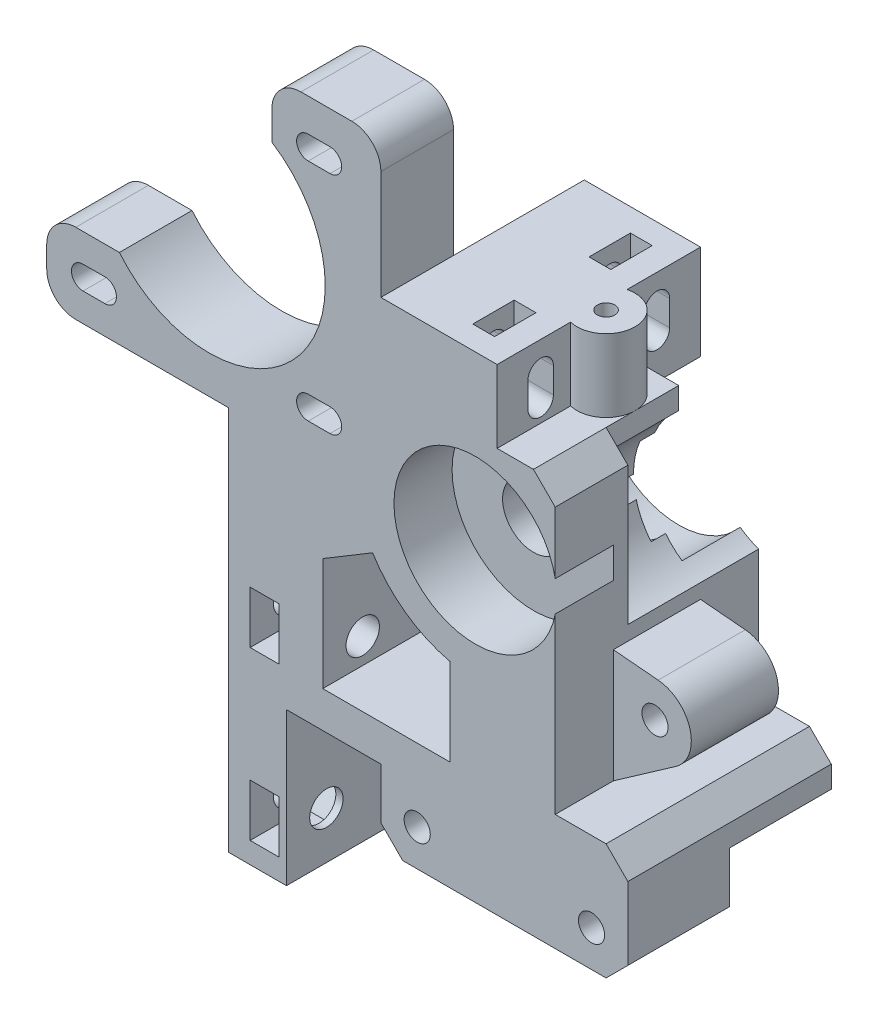
SolidWorks part; units mm, degrees
ref_plane "Front Plane" through (0, 0, 0) normal (0, 0, 1) x (1, 0, 0)
ref_plane "Top Plane" through (0, 0, 0) normal (0, 1, 0) x (1, 0, 0)
ref_plane "Right Plane" through (0, 0, 0) normal (1, 0, 0) x (0, 0, -1)
sketch "Sketch1" plane through (0, 0, 0) normal (0, 0, 1) x (1, 0, 0)
  line L0 (0, 0) -> (0, -11)
  line L1 (0, -11) -> (25, -11)
  line L2 (25, -11) -> (25, -64)
  line L3 (25, -64) -> (33, -64)
  line L4 (33, -64) -> (33, -43)
  line L5 (33, -43) -> (46, -43)
  line L6 (46, -43) -> (46, -53)
  line L7 (46, -53) -> (85, -53)
  line L8 (85, -53) -> (85, -43) construction
  line L9 (85, -43) -> (80, -43)
  line L10 (80, -43) -> (80, -37)
  line L11 (80, -37) -> (70, -37)
  line L12 (70, -37) -> (78.6011, -30.9774)
  line L13 (70, -37) -> (70, -21.361) construction
  line L14 (70, -21.361) -> (76.169, -21.9007)
  line L15 (70, -21.361) -> (70, 12.639)
  line L16 (70, 12.639) -> (46, 12.639)
  line L17 (46, 12.639) -> (46, 31.639)
  line L18 (46, 31.639) -> (31, 31.639)
  line L19 (31, 31.639) -> (31, 23.639)
  line L20 (0, 0) -> (10, 0)
  line L21 (38, -22.5) -> (38, -38)
  line L22 (38, -38) -> (55.5, -38)
  line L23 (55.5, -38) -> (55.5, -26)
  line L24 (38, -22.5) -> (44.8573, -18.3797)
  line L25 (85, -48) -> (46, -48) construction
  line L26 (25, -11) -> (59, -11) construction
  line L27 (5, -5.5) -> (8, -5.5) construction
  line L28 (5, -3.9) -> (8, -3.9)
  line L29 (5, -7.1) -> (8, -7.1)
  line L30 (36, -5.5) -> (39, -5.5) construction
  line L31 (36, -3.9) -> (39, -3.9)
  line L32 (36, -7.1) -> (39, -7.1)
  line L33 (36, 25.5) -> (39, 25.5) construction
  line L34 (36, 27.1) -> (39, 27.1)
  line L35 (36, 23.9) -> (39, 23.9)
  line L36 (5, -5.5) -> (36, -5.5) construction
  line L37 (36, -5.5) -> (36, 25.5) construction
  line L38 (5, -5.5) -> (0, -5.5) construction
  arc A0 (85, -53) -> (85, -43) centre (85, -48) ccw
  circle A1 centre (75.7332, -26.8817) radius 5
  arc A2 (10, 0) -> (31, 23.639) centre (22.3388, 10.186) ccw
  arc A3 (44.8573, -18.3797) -> (55.5, -26) centre (59.3127, -9.4331) ccw
  circle A4 centre (51, -48) radius 1.8
  circle A5 centre (75, -48) radius 1.8
  circle A6 centre (85, -48) radius 1.8
  circle A7 centre (75.7332, -26.8817) radius 1.8
  circle A8 centre (59, -11) radius 4.25
  arc A9 (5, -3.9) -> (5, -7.1) centre (5, -5.5) ccw
  arc A10 (8, -7.1) -> (8, -3.9) centre (8, -5.5) ccw
  arc A11 (36, -3.9) -> (36, -7.1) centre (36, -5.5) ccw
  arc A12 (39, -7.1) -> (39, -3.9) centre (39, -5.5) ccw
  arc A13 (36, 27.1) -> (36, 23.9) centre (36, 25.5) ccw
  arc A14 (39, 23.9) -> (39, 27.1) centre (39, 25.5) ccw
  point P45 (6.5, -5.5)
  point P50 (37.5, -5.5)
  point P57 (37.5, 25.5)
  dimension "D1" = 11
  dimension "D14" = 35
  dimension "D9" = 10
  dimension "D15" = 10
  dimension "D21" = 10
  dimension "D28" = 17
  dimension "D31" = 3.6
  dimension "D33" = 24
  dimension "D34" = 34
  dimension "D35" = 8.5
  dimension "D37" = 1.6
  dimension "D39" = 5
  dimension "D40" = 16
  dimension "D2" = 25
  dimension "D4" = 8
  dimension "D5" = 21
  dimension "D6" = 13
  dimension "D7" = 10
  dimension "D8" = 39
  dimension "D10" = 5
  dimension "D11" = 6
  dimension "D12" = 10
  dimension "D13" = 10.5
  dimension "D16" = 40
  dimension "D17" = 34
  dimension "D18" = 24
  dimension "D19" = 19
  dimension "D20" = 15
  dimension "D22" = 8
  dimension "D23" = 15.5
  dimension "D24" = 17.5
  dimension "D25" = 12
  dimension "D26" = 8
  dimension "D27" = 121
  dimension "D29" = 5
  dimension "D30" = 5
  dimension "D32" = 5
  dimension "D36" = 3
  dimension "D38" = 31
  dimension "D41" = 53
extrude "Boss-Extrude1" add sketch "Sketch1" against normal blind 34 contours A2 L20 L0 L1 L2 L3 L4 L5 L6 L7 A0 L9 L10 L11 L12 A1 L14 L15 L16 L17 L18 L19 A14 L35 A13 L34 A12 L32 A11 L31 A10 L29 A9 L28 A8 A6 A5 A4 L24 A3 L23 L22 L21 | A1 A7 region at (48.0686, -19.084, 0) region at (79.3153, -23.5993, 0)
sketch "Sketch7" plane through (0, 0, 0) normal (0, 0, 1) x (1, 0, 0)
  line L1 (70, -21.361) -> (80.7332, -21.361)
  line L2 (70, -21.361) -> (70, -37)
  line L3 (70, -37) -> (80.7332, -37)
  line L4 (80.7332, -21.361) -> (80.7332, -37)
  circle A0 centre (59, -11) radius 11.2
  arc A1 (78.6011, -30.9774) -> (76.169, -21.9007) centre (75.7332, -26.8817) ccw construction
  dimension "D1" = 22.4
extrude "Cut-Extrude5" cut sketch "Sketch7" against normal blind 8
sketch "Sketch2" plane through (25, 0, 0) normal (-1, 0, 0) x (0, 0, 1)
  line L0 (-28.5, -34.5) -> (-5.5, -34.5) construction
  line L1 (-5.5, -34.5) -> (-5.5, -57.5) construction
  line L2 (-5.5, -57.5) -> (-28.5, -57.5) construction
  line L3 (-28.5, -57.5) -> (-28.5, -34.5) construction
  line L4 (-17, -57.5) -> (-17, -64) construction
  line L5 (-34, -64) -> (0, -64) construction
  line L6 (-34, -24) -> (-28, -24)
  line L7 (-34, -11) -> (-34, -64) construction
  line L8 (-28, -24) -> (-28, 13.5)
  line L9 (-28, 13.5) -> (-10, 13.5)
  line L10 (-10, 13.5) -> (-10, 31.639)
  line L11 (-34, 31.639) -> (0, 31.639) construction
  line L12 (-10, 31.639) -> (-34, 31.639)
  line L13 (-34, 31.639) -> (-34, -24)
  circle A0 centre (-28.5, -34.5) radius 2.3
  circle A1 centre (-5.5, -34.5) radius 2.3
  circle A2 centre (-5.5, -57.5) radius 2.3
  circle A3 centre (-28.5, -57.5) radius 2.3
  dimension "D3" = 4.6
  dimension "D1" = 23
  dimension "D2" = 6.5
  dimension "D4" = 6
  dimension "D5" = 37.5
  dimension "D6" = 18
  dimension "D7" = 40
extrude "Cut-Extrude1" cut sketch "Sketch2" against normal blind 28
sketch "Sketch4" plane through (0, 0, -34) normal (0, 0, -1) x (-1, 0, 0)
  line L0 (-25, -24) -> (-46, -11.3806)
  line L1 (-46, -11.3806) -> (-46, 31.639)
  line L2 (-46, 31.639) -> (0, 31.639)
  line L3 (0, 31.639) -> (0, -11)
  line L4 (0, -11) -> (-25, -11)
  line L5 (-25, -11) -> (-25, -24)
  line L6 (-70, 12.639) -> (-67, 12.639)
  line L7 (-46, -53) -> (-85, -53) construction
  line L8 (-70, 12.639) -> (-70, -19.361)
  line L9 (-70, -21.361) -> (-70, 12.639) construction
  line L10 (-80, -43) -> (-90, -43)
  line L11 (-67, 12.639) -> (-67, -0.361)
  line L12 (-80, -43) -> (-80, -53)
  line L13 (-80, -53) -> (-90, -53)
  line L14 (-90, -43) -> (-90, -53)
  arc A0 (-70, -19.361) -> (-67, -0.361) centre (-73.7732, -9.0284) ccw
  arc A1 (-85, -43) -> (-85, -53) centre (-85, -48) ccw construction
  dimension "D4" = 11
  dimension "D1" = 24.5
  dimension "D2" = 3
  dimension "D3" = 32
  dimension "D5" = 13
extrude "Cut-Extrude2" cut sketch "Sketch4" against normal blind 24
sketch "Sketch5" plane through (0, 0, -34) normal (0, 0, -1) x (-1, 0, 0)
  line L0 (-33, -24) -> (-33, -64)
  line L1 (-25, -24) -> (-38, -24) construction
  line L2 (-33, -24) -> (0, -24)
  line L3 (0, -24) -> (0, 31.639)
  line L4 (0, 31.639) -> (-90, 31.639)
  line L5 (-90, 31.639) -> (-90, -64)
  line L6 (-90, -64) -> (-33, -64)
  line L7 (-46, 31.639) -> (-31, 31.639) construction
  line L9 (-25, -64) -> (-33, -64) construction
  line L10 (-33, -64) -> (-33, -43) construction
  arc A0 (-85, -43) -> (-85, -53) centre (-85, -48) ccw construction
extrude "Cut-Extrude3" cut sketch "Sketch5" against normal blind 6 contours L5 L6 L0 L2 L3 L4
sketch "Sketch6" plane through (0, 0, -34) normal (0, 0, -1) x (-1, 0, 0)
  line L0 (-67, 12.639) -> (-67, -3.4502)
  line L1 (-70, -21.361) -> (-80.7332, -21.361)
  line L2 (-70, -21.361) -> (-70, -37)
  line L3 (-70, -37) -> (-80.7332, -37)
  line L4 (-80.7332, -21.361) -> (-80.7332, -37)
  line L5 (-67, -0.361) -> (-67, 12.639) construction
  line L6 (-67, 12.639) -> (-62, 12.639)
  line L7 (-46, 12.639) -> (-67, 12.639) construction
  line L8 (-62, 12.639) -> (-62, -0.417)
  circle A0 centre (-59, -11) radius 11
  arc A1 (-76.169, -21.9007) -> (-78.6011, -30.9774) centre (-75.7332, -26.8817) ccw construction
  dimension "D1" = 22
  dimension "D2" = 5
extrude "Cut-Extrude4" cut sketch "Sketch6" against normal blind 14 contours A0 L8 L6 L0 | A0 | L1 L4 L3 L2 region at (64.5868, 5.4811, -34) region at (59, -11, -34) region at (75.3666, -29.1805, -34)
sketch "Sketch8" plane through (0, 0, -28) normal (0, 0, -1) x (-1, 0, 0)
  line L1 (-46, -53) -> (-80, -53)
  line L2 (-46, -53) -> (-46, -43)
  line L3 (-46, -43) -> (-80, -43)
  line L4 (-80, -53) -> (-80, -43)
extrude "Cut-Extrude7" cut sketch "Sketch8" against normal blind 14
sketch "Sketch9" plane through (0, 0, -20) normal (0, 0, -1) x (-1, 0, 0)
  circle A0 centre (-59, -11) radius 7.9
  dimension "D1" = 15.8
extrude "Cut-Extrude8" cut sketch "Sketch9" against normal blind 2
sketch "Sketch10" plane through (0, 12.639, 0) normal (0, 1, 0) x (1, 0, 0)
  line L0 (70, 10) -> (70, 0)
  line L1 (70, 8) -> (70, 0) construction
  line L2 (57, 3.15) -> (57, 0) construction
  line L3 (55.5, 24.85) -> (58.5, 24.85)
  line L4 (55.5, 24.85) -> (55.5, 19.15)
  line L5 (55.5, 19.15) -> (58.5, 19.15)
  line L6 (58.5, 24.85) -> (58.5, 19.15)
  line L7 (55.5, 8.85) -> (58.5, 8.85)
  line L8 (55.5, 8.85) -> (55.5, 3.15)
  line L9 (55.5, 3.15) -> (58.5, 3.15)
  line L10 (58.5, 8.85) -> (58.5, 3.15)
  line L11 (57, 24.85) -> (57, 28) construction
  line L12 (57, 8.85) -> (57, 19.15) construction
  line L14 (70, 0) -> (46, 0) construction
  line L15 (70, 10) -> (67, 10)
  line L16 (67, 10) -> (67, 20)
  line L17 (67, 20) -> (62, 20)
  line L18 (67.4569, 20) -> (48, 20) construction
  line L19 (62, 20) -> (62, 17.873)
  line L20 (62, 17.873) -> (62, 10.127) construction
  line L21 (63, 14) -> (57, 14) construction
  line L22 (70, 0) -> (62, 0)
  line L23 (62, 0) -> (62, 10.127)
  line L24 (46, 28) -> (62, 28) construction
  arc A0 (62, 17.873) -> (62, 10.127) centre (63, 14) cw
  line M9 (67, 20) -> (62, 20)
  line M15 (70, 0) -> (70, 10)
  line M16 (70, 10) -> (67, 10)
  line M17 (67, 10) -> (67, 20)
  dimension "D5" = 4
  dimension "D2" = 5.7
  dimension "D3" = 3
  dimension "D4" = 3.15
  dimension "D6" = 5
extrude "Cut-Extrude9" cut sketch "Sketch10" against normal blind 10 contours L6 L3 L4 L5 | L19 A0 L16 M9 | A0 L23 L22 M17 M15 M16 | L8 L9 L10 L7 region at (64.9023, 12.639, -18.5143) region at (66.0025, 12.639, -5.245) region at (57, 12.639, -22)
sketch "Sketch11" plane through (0, -53, 0) normal (0, -1, 0) x (1, 0, 0)
  line L0 (46, -14) -> (80, -14) construction
  circle A0 centre (63, -14) radius 1.2
  dimension "D1" = 2.4
extrude "Cut-Extrude10" cut sketch "Sketch11" against normal through all both and the other way through all
sketch "Sketch12" plane through (0, -53, 0) normal (0, -1, 0) x (1, 0, 0)
  circle A0 centre (63, -14) radius 8.1
  dimension "D1" = 16.2
extrude "Cut-Extrude11" cut sketch "Sketch12" against normal up to surface (10 mm away) from offset 5.5 up to face at (55.5, -43, -14.15) offset against normal yes
sketch "Sketch13" plane through (0, -53, 0) normal (0, -1, 0) x (1, 0, 0)
  circle A0 centre (63, -14) radius 6.1
  dimension "D1" = 12.2
extrude "Cut-Extrude12" cut sketch "Sketch13" against normal up to surface (5.5 mm away) up to face at (63, -47.5, -11.675)
sketch "Sketch15" plane through (62, 0, 0) normal (1, 0, 0) x (0, 0, -1)
  line L0 (6, 8.639) -> (6, 5.139) construction
  line L1 (7.75, 8.639) -> (7.75, 5.139)
  line L2 (4.25, 8.639) -> (4.25, 5.139)
  line L3 (22, 8.639) -> (22, 5.139) construction
  line L4 (23.75, 8.639) -> (23.75, 5.139)
  line L5 (20.25, 8.639) -> (20.25, 5.139)
  line L6 (6, 6.889) -> (22, 6.889) construction
  line L7 (6, 8.639) -> (6, 12.639) construction
  line L9 (10, 12.639) -> (0, 12.639) construction
  line L10 (10, 12.639) -> (10, 2.639) construction
  arc A0 (7.75, 8.639) -> (4.25, 8.639) centre (6, 8.639) ccw
  arc A1 (4.25, 5.139) -> (7.75, 5.139) centre (6, 5.139) ccw
  arc A2 (23.75, 8.639) -> (20.25, 8.639) centre (22, 8.639) ccw
  arc A3 (20.25, 5.139) -> (23.75, 5.139) centre (22, 5.139) ccw
  point P2 (6, 6.889)
  point P11 (22, 6.889)
  dimension "D2" = 1.75
  dimension "D1" = 3.5
  dimension "D3" = 4
  dimension "D4" = 16
  dimension "D5" = 4
extrude "Cut-Extrude14" cut sketch "Sketch15" against normal up to surface (16 mm away) up to face at (46, 0.6292, -19)
ref_plane "Plane1" through (28, 0, 0) normal (-1, 0, 0) x (0, 0, 1)
sketch "Sketch16" plane through (28, 0, 0) normal (-1, 0, 0) x (0, 0, 1)
  line L0 (-30.5785, -53.9) -> (-34, -53.9)
  line L1 (-24.3431, -34.5) -> (-26.4215, -30.9)
  line L2 (-26.4215, -30.9) -> (-30.5785, -30.9)
  line L3 (-30.5785, -30.9) -> (-32.6569, -34.5)
  line L4 (-32.6569, -34.5) -> (-30.5785, -38.1)
  line L5 (-30.5785, -38.1) -> (-26.4215, -38.1)
  line L6 (-26.4215, -38.1) -> (-24.3431, -34.5)
  line L7 (-24.3431, -57.5) -> (-26.4215, -53.9)
  line L8 (-26.4215, -53.9) -> (-30.5785, -53.9)
  line L9 (-30.5785, -53.9) -> (-32.6569, -57.5)
  line L10 (-32.6569, -57.5) -> (-30.5785, -61.1)
  line L11 (-30.5785, -61.1) -> (-26.4215, -61.1)
  line L12 (-26.4215, -61.1) -> (-24.3431, -57.5)
  line L13 (-9.6569, -57.5) -> (-7.5785, -61.1)
  line L14 (-7.5785, -61.1) -> (-3.4215, -61.1)
  line L15 (-3.4215, -61.1) -> (-1.3431, -57.5)
  line L16 (-1.3431, -57.5) -> (-3.4215, -53.9)
  line L17 (-3.4215, -53.9) -> (-7.5785, -53.9)
  line L18 (-7.5785, -53.9) -> (-9.6569, -57.5)
  line L19 (-9.6569, -34.5) -> (-7.5785, -38.1)
  line L20 (-7.5785, -38.1) -> (-3.4215, -38.1)
  line L21 (-3.4215, -38.1) -> (-1.3431, -34.5)
  line L22 (-1.3431, -34.5) -> (-3.4215, -30.9)
  line L23 (-3.4215, -30.9) -> (-7.5785, -30.9)
  line L24 (-7.5785, -30.9) -> (-9.6569, -34.5)
  line L25 (-34, -24) -> (-34, -64) construction
  line L26 (-34, -53.9) -> (-34, -61.1)
  line L27 (-34, -61.1) -> (-30.5785, -61.1)
  line L28 (-30.5785, -30.9) -> (-34, -30.9)
  line L29 (-34, -30.9) -> (-34, -38.1)
  line L30 (-34, -38.1) -> (-30.5785, -38.1)
  line L31 (-3.4215, -30.9) -> (0, -30.9)
  line L32 (0, -11) -> (0, -64) construction
  line L33 (0, -30.9) -> (0, -38.1)
  line L34 (0, -38.1) -> (-3.4215, -38.1)
  line L35 (-3.4215, -53.9) -> (0, -53.9)
  line L36 (0, -53.9) -> (0, -61.1)
  line L37 (0, -61.1) -> (-3.4215, -61.1)
  circle A0 centre (-28.5, -34.5) radius 3.6 construction
  circle A1 centre (-28.5, -57.5) radius 3.6 construction
  circle A2 centre (-5.5, -57.5) radius 3.6 construction
  circle A3 centre (-5.5, -34.5) radius 3.6 construction
  dimension "D1" = 7.2
extrude "Cut-Extrude15" cut sketch "Sketch16" against normal blind 4 contours L29 L30 L4 L3 L28 | L5 L6 L1 L2 L3 L4 | L26 L27 L10 L9 L0 | L11 L12 L7 L8 L9 L10 | L23 L24 L19 L20 L21 L22 | L34 L33 L31 L22 L21 | L17 L18 L13 L14 L15 L16 | L37 L36 L35 L16 L15 region at (28, -57.5, -32.7333) region at (28, -57.5, -28.5) region at (28, -34.5, -28.5) region at (28, -34.5, -32.7333) region at (28, -57.5, -5.5) region at (28, -57.5, -1.2667) region at (28, -34.5, -5.5) region at (28, -34.5, -1.2667)
fillet "Fillet1" radius 4 6 edges at (31, 31.639, -5) (46, 31.639, -5) (0, 0, -5) (0, -11, -5) (29, -24, -34) (29, -64, -34)
sketch "Sketch17" plane through (0, 0, -10) normal (0, 0, -1) x (-1, 0, 0)
  line L0 (-80, -43) -> (-85, -43) construction
  line L1 (-80, -53) -> (-90, -53)
  line L2 (-80, -53) -> (-80, -43)
  line L3 (-80, -43) -> (-90, -43)
  line L4 (-90, -53) -> (-90, -43)
  arc A0 (-85, -43) -> (-85, -53) centre (-85, -48) ccw construction
  point P4 (0, 0)
extrude "fail" cut sketch "Sketch17" against normal through all both and the other way through all
chamfer "Chamfer1" distance 3 angle 45 4 edges at (46, -53, -7) (80, -53, -7) (70, 2.639, -5) (80, -37, -14)
